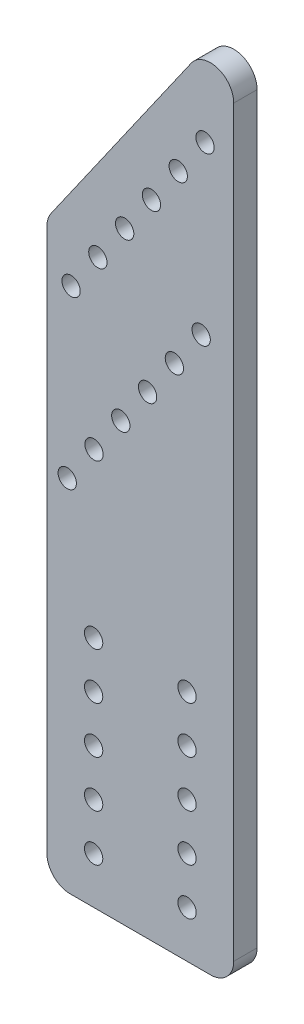
SolidWorks part; units mm, degrees
material "6061-T6 (SS)"
ref_plane "Front Plane" through (0, 0, 0) normal (0, 0, 1) x (1, 0, 0)
ref_plane "Top Plane" through (0, 0, 0) normal (0, 1, 0) x (1, 0, 0)
ref_plane "Right Plane" through (0, 0, 0) normal (1, 0, 0) x (0, 0, -1)
sketch "Sketch1" plane through (0, 0, 0) normal (0, 0, 1) x (1, 0, 0)
  line L0 (0, 156.0501) -> (50.8, 228.6)
  line L1 (0, 0) -> (50.8, 0)
  line L2 (0, 0) -> (0, 156.0501)
  line L3 (0, 228.6) -> (50.8, 228.6) construction
  line L4 (50.8, 0) -> (50.8, 228.6)
  line L5 (0, 156.0501) -> (0, 228.6) construction
  dimension "D1" = 50.8
  dimension "D2" = 55
  dimension "D3" = 228.6
extrude "Boss-Extrude1" add sketch "Sketch1" along normal blind 6.35
sketch "Sketch2" plane through (0, 0, 0) normal (0, 0, -1) x (-1, 0, 0)
  line L2 (-50.8, 12.7) -> (0, 12.7) construction
  line L3 (-50.8, 0) -> (-50.8, 228.6) construction
  line L4 (0, 156.0501) -> (0, 0) construction
  line L5 (0, 0) -> (-50.8, 0) construction
  line L6 (-50.8, 228.6) -> (-92.4129, 199.4623) construction
  line L7 (-50.8, 228.6) -> (0, 156.0501) construction
  line L8 (-92.4129, 199.4623) -> (-41.6129, 126.9124) construction
  line L9 (0, 156.0501) -> (-41.6129, 126.9124) construction
  line L10 (-50.8, 228.6) -> (0, 156.0501) construction
  line L11 (-88.7707, 194.2607) -> (-47.1578, 223.3984) construction
  circle A33 centre (-38.1, 12.7) radius 2.4892
  circle A34 centre (-12.7, 12.7) radius 2.4892
  circle A35 centre (-12.7, 25.4) radius 2.4892
  circle A36 centre (-38.1, 25.4) radius 2.4892
  circle A37 centre (-12.7, 38.1) radius 2.4892
  circle A38 centre (-38.1, 38.1) radius 2.4892
  circle A39 centre (-12.7, 50.8) radius 2.4892
  circle A40 centre (-38.1, 50.8) radius 2.4892
  circle A41 centre (-12.7, 63.5) radius 2.4892
  circle A42 centre (-38.1, 63.5) radius 2.4892
  circle A43 centre (-78.3675, 201.5451) radius 2.4892 construction
  circle A44 centre (-57.561, 216.114) radius 2.4892 construction
  circle A45 centre (-50.2766, 205.7107) radius 2.4892 construction
  circle A46 centre (-71.0831, 191.1419) radius 2.4892 construction
  circle A47 centre (-42.9922, 195.3075) radius 2.4892
  circle A48 centre (-63.7986, 180.7387) radius 2.4892 construction
  circle A49 centre (-35.7078, 184.9043) radius 2.4892
  circle A50 centre (-56.5142, 170.3354) radius 2.4892 construction
  circle A51 centre (-28.4233, 174.501) radius 2.4892
  circle A52 centre (-49.2298, 159.9322) radius 2.4892 construction
  circle A53 centre (-21.1389, 164.0978) radius 2.4892
  circle A54 centre (-41.9454, 149.529) radius 2.4892
  circle A55 centre (-13.8545, 153.6946) radius 2.4892
  circle A56 centre (-34.661, 139.1257) radius 2.4892
  circle A57 centre (-6.5701, 143.2913) radius 2.4892
  circle A58 centre (-27.3765, 128.7225) radius 2.4892
  circle A59 centre (0.7143, 132.8881) radius 2.4892 construction
  circle A60 centre (-20.0921, 118.3193) radius 2.4892
  circle A61 centre (7.9988, 122.4849) radius 2.4892 construction
  circle A62 centre (-12.8077, 107.916) radius 2.4892
  circle A63 centre (15.2832, 112.0817) radius 2.4892 construction
  circle A64 centre (-5.5233, 97.5128) radius 2.4892
  circle A65 centre (22.5676, 101.6784) radius 2.4892 construction
  circle A66 centre (1.7611, 87.1096) radius 2.4892 construction
  dimension "D1" = 12.7
  dimension "D2" = 25.4
  dimension "D3" = 4.9784
  dimension "D4" = 12.7
  dimension "D5" = 12.7
  dimension "D6" = 50.8
  dimension "D8" = 12.7
  dimension "D9" = 25.4
  dimension "D10" = 6.35
  dimension "D11" = 12.7
  dimension "D7" = 5
  dimension "D12" = 12
extrude "Cut-Extrude1" cut sketch "Sketch2" against normal through all
fillet "Fillet1" radius 6.35 4 edges at (0, 156.0501, 3.175) (50.8, 0, 3.175) (0, 0, 3.175) (50.8, 228.6, 3.175)
